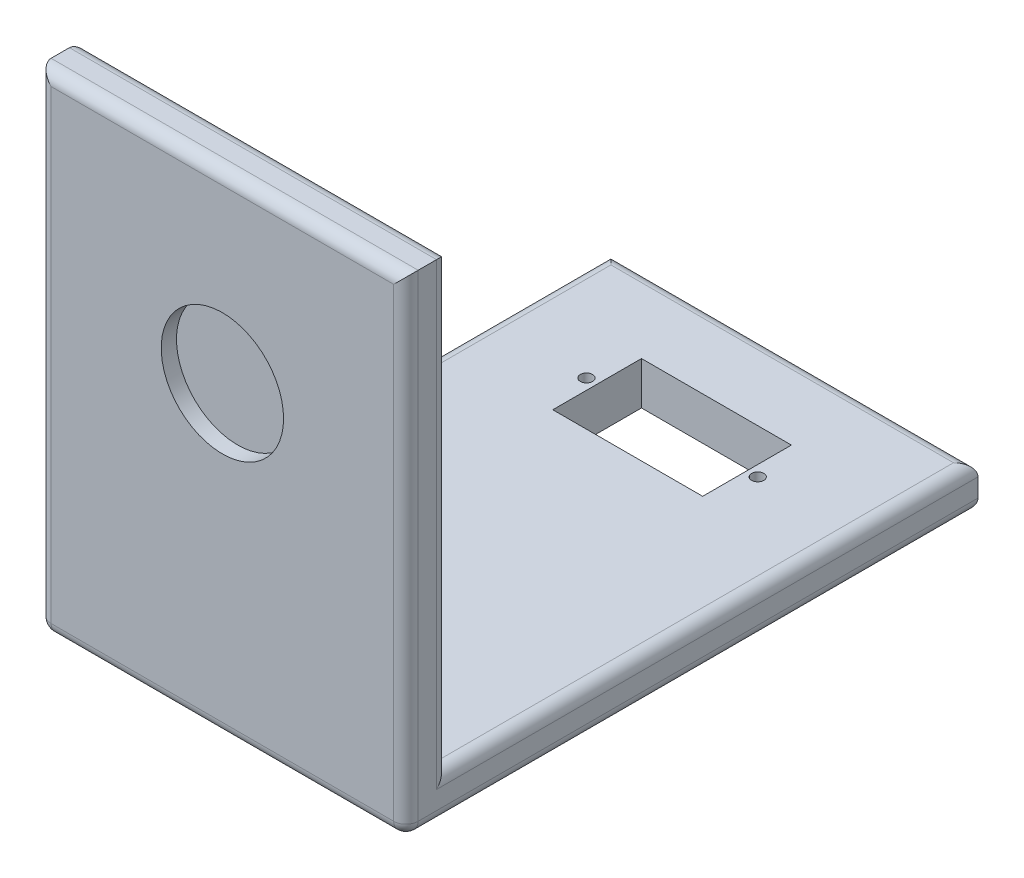
SolidWorks part; units mm, degrees
ref_plane "Alzado" through (0, 0, 0) normal (0, 0, 1) x (1, 0, 0)
ref_plane "Planta" through (0, 0, 0) normal (0, 1, 0) x (1, 0, 0)
ref_plane "Vista lateral" through (0, 0, 0) normal (1, 0, 0) x (0, 0, -1)
sketch "Croquis1" plane through (0, 0, 0) normal (0, 1, 0) x (1, 0, 0)
  line L0 (0, 0) -> (0, 40015.7255) construction
  line L1 (0, 0) -> (40015.7255, 0) construction
  line L3 (-30, -45) -> (30, -45)
  line L4 (-30, -45) -> (-30, 45)
  line L5 (-30, 45) -> (30, 45)
  line L6 (30, -45) -> (30, 45)
  line L7 (-30, -45) -> (30, 45) construction
  line L8 (-30, 45) -> (30, -45) construction
  point P5 (0, 0)
  dimension "D1" = 60
  dimension "D2" = 90
extrude "Base" add sketch "Croquis1" along normal blind 3.5 and the other way blind 3.5
sketch "Croquis2" plane through (0, 3.5, 0) normal (0, 1, 0) x (1, 0, 0)
  line L0 (0, 0) -> (0, 50000) construction
  line L1 (0, 0) -> (50000, 0) construction
  line L3 (-12.25, 17.75) -> (12.25, 17.75)
  line L4 (-12.25, 17.75) -> (-12.25, 32.25)
  line L5 (-12.25, 32.25) -> (12.25, 32.25)
  line L6 (12.25, 17.75) -> (12.25, 32.25)
  line L7 (-12.25, 17.75) -> (12.25, 32.25) construction
  line L8 (-12.25, 32.25) -> (12.25, 17.75) construction
  line L9 (30, 45) -> (-30, 45) construction
  circle A2 centre (-14, 25) radius 1
  circle A3 centre (14, 25) radius 1
  point P5 (0, 25)
  dimension "D3" = 2
  dimension "D4" = 14
  dimension "D1" = 24.5
  dimension "D2" = 14.5
  dimension "D5" = 20
extrude "Agujero Servo" cut sketch "Croquis2" against normal up to next
sketch "Croquis3" plane through (0, 0, 45) normal (0, 0, 1) x (1, 0, 0)
  line L0 (0, 0) -> (0, 50000) construction
  line L1 (0, 0) -> (50000, 0) construction
  line L2 (-30, -3.5) -> (-30, 3.5) construction
  line L3 (-30, -3.5) -> (30, -3.5)
  line L4 (-30, -3.5) -> (-30, 76.5)
  line L5 (-30, 76.5) -> (30, 76.5)
  line L6 (30, -3.5) -> (30, 76.5)
  line L7 (30, -3.5) -> (30, 3.5) construction
  line L9 (-30, -3.5) -> (30, -3.5) construction
  point P9 (0, 0)
  dimension "D1" = 80
extrude "Pared" add sketch "Croquis3" along normal blind 3.5 and the other way blind 3.5
fillet "Redondeo2" radius 2 13 edges at (0, 76.5, 48.5) (30, 36.5, 48.5) (0, -3.5, 48.5) (-30, 36.5, 48.5) (-30, 40, 41.5) (30, 40, 41.5) (0, 76.5, 41.5) (30, -3.5, 1.75) (30, 3.5, -1.75) (0, -3.5, -45) (0, 3.5, -45) (-30, -3.5, 1.75) (-30, 3.5, -1.75)
sketch "Croquis4" plane through (0, 0, 48.5) normal (0, 0, 1) x (1, 0, 0)
  line L0 (0, 0) -> (0, 50000) construction
  line L2 (-30, 76.5) -> (30, 76.5) construction
  circle A0 centre (0, 46.5) radius 10
  dimension "D1" = 20
  dimension "D2" = 30
extrude "RecorteNuevoServo" cut sketch "Croquis4" against normal blind 2.5
